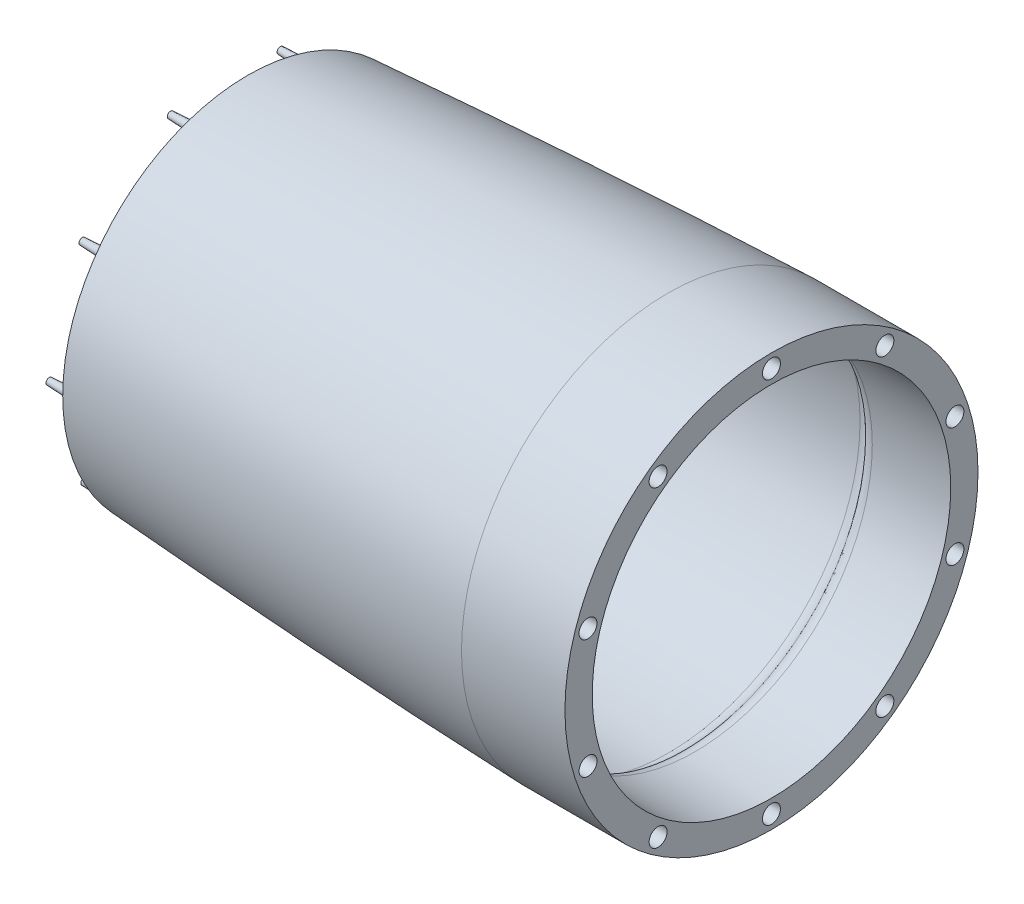
SolidWorks part; units mm, degrees
ref_plane "Front Plane" through (0, 0, 0) normal (0, 0, 1) x (1, 0, 0)
ref_plane "Top Plane" through (0, 0, 0) normal (0, 1, 0) x (1, 0, 0)
ref_plane "Right Plane" through (0, 0, 0) normal (1, 0, 0) x (0, 0, -1)
sketch "Sketch1" plane through (0, 0, 0) normal (0, 0, 1) x (1, 0, 0)
  line L2 (0, -76.2) -> (-921.7152, -76.2) construction
  line L3 (6.35, 6.35) -> (6.35, 0)
  line L4 (-259.8125, 11.4606) -> (6.35, 11.4606)
  line L5 (0, 0) -> (6.35, 0)
  line L6 (6.35, 6.35) -> (6.35, -76.2) construction
  line L7 (0, 0) -> (0, -76.2) construction
  line L8 (-921.7152, -58.5997) -> (-928.0652, -58.5997)
  line L9 (-928.0652, -58.5997) -> (-928.0652, -76.2) construction
  line L10 (-921.7152, -58.5997) -> (-921.7152, -76.2) construction
  line L11 (6.35, 11.4606) -> (6.35, 6.35)
  arc A0 (-254, 2.1118) -> (-248.4137, -0.891) centre (-248.6021, 5.4563) ccw
  arc A2 (-916.3053, -52.3197) -> (-921.7152, -58.5997) centre (-915.3652, -58.5997) ccw
  arc A4 (-254, 2.1118) -> (-259.6052, 5.114) centre (-259.3979, -1.2327) ccw
  arc A6 (-248.6021, 5.4563) -> (-248.6021, 5.4563) centre (-248.6021, 5.4563) ccw
  arc A7 (-248.6021, 5.4563) -> (-259.8125, 11.4606) centre (-259.3979, -1.2327) ccw
  arc A8 (-917.2454, -46.0396) -> (-928.0652, -58.5997) centre (-915.3652, -58.5997) ccw
  spline S0 degree 3 poles (0, 0) (-50.8, 0) (-101.6, 0) (-157.1824, 0) (-166.7471, 0) (-181.0943, 0) (-190.659, 0) (-199.5851, 0) (-207.8726, 0) (-220.3048, -0.155) (-228.5897, -0.3615) (-235.0947, -0.5237) (-239.8196, -0.6415) (-245.0466, -0.7915) (-247.9113, -0.876) (-248.4137, -0.891) knots 0.761574 0.761574 0.761574 0.761574 0.907842 0.907842 0.921611 0.935381 0.949151 0.949151 0.961082 0.973013 0.984944 0.984944 0.991748 0.998553 1 1 1 1
  spline S1 degree 1 poles (6.35, 6.35) (-248.6021, 5.4563) knots 0 0 1 1 construction
  spline S2 degree 3 poles (-259.6052, 5.114) (-267.1277, 4.8682) (-283.426, 4.2857) (-317.2703, 2.8805) (-361.13, 0.7112) (-431.2755, -3.372) (-501.3729, -8.2669) (-571.4145, -13.8917) (-623.9147, -18.4777) (-676.3803, -23.4393) (-728.8057, -28.7991) (-772.4536, -33.6275) (-807.3418, -37.7392) (-833.4907, -40.9589) (-859.6194, -44.3289) (-885.7239, -47.8693) (-904.6125, -50.5779) (-914.801, -52.0945) (-916.3053, -52.3197) knots 0.121539 0.121539 0.121539 0.121539 0.143123 0.168303 0.218664 0.269025 0.369746 0.420107 0.470467 0.520828 0.571189 0.62155 0.64673 0.67191 0.697091 0.722271 0.747451 0.751814 0.751814 0.751814 0.751814
  spline S3 degree 1 poles (-259.8125, 11.4606) (-917.2454, -46.0396) knots 0 0 1 1 construction
  spline S4 degree 3 poles (6.35, 6.35) (-14.881, 6.35) (-57.3424, 6.3506) (-110.4226, 6.3484) (-152.8795, 6.3528) (-179.4314, 6.3414) (-200.6356, 6.3648) (-216.6826, 6.282) (-232.6614, 5.8947) (-243.2867, 5.614) (-248.6021, 5.4563) knots 0.75548 0.75548 0.75548 0.75548 0.81661 0.87774 0.908305 0.93887 0.954152 0.969435 0.984717 1 1 1 1
  spline S5 degree 3 poles (-259.8125, 11.4606) (-287.3121, 10.5623) (-342.298, 8.1716) (-452.1401, 1.8335) (-589.2803, -8.5121) (-726.1766, -21.7709) (-835.4658, -34.5887) (-890.027, -41.9652) (-917.2454, -46.0396) knots 0.121539 0.121539 0.121539 0.121539 0.200324 0.279108 0.436676 0.594245 0.673029 0.751814 0.751814 0.751814 0.751814
revolve "Revolve1" add sketch "Sketch1" angle 360 about L2 region at (-124.3289, 8.8839, 0) region at (-3.0204, 3.175, 0)
ref_plane "Plane1" through (-215.9, 0, 0) normal (1, 0, 0) x (0, 0, -1)
sketch "Sketch2" plane through (-215.9, 0, 0) normal (1, 0, 0) x (0, 0, -1)
  circle A0 centre (0, -76.2) radius 87.6606 construction
  circle A1 centre (0, -76.2) radius 87.6606 construction
  circle A2 centre (0, -76.2) radius 110.1147
extrude "Cut-Extrude1" cut sketch "Sketch2" along normal through all contours A2 region at (-215.9, -76.2, 0)
ref_plane "Plane2" through (-438.15, 0, 0) normal (1, 0, 0) x (0, 0, -1)
sketch "Sketch5" plane through (-438.15, 0, 0) normal (1, 0, 0) x (0, 0, -1)
  circle A0 centre (0, -76.2) radius 87.6606 construction
  circle A1 centre (0, -76.2) radius 87.6606 construction
  circle A2 centre (0, -76.2) radius 128.8001
extrude "Cut-Extrude2" cut sketch "Sketch5" against normal through all
sketch "Sketch6" plane through (-215.9, 0, 0) normal (1, 0, 0) x (0, 0, -1)
  circle A0 centre (0, -76.2) radius 76.0918 construction
  circle A1 centre (0, -76.2) radius 87.6606 construction
  circle A2 centre (0, -76.2) radius 76.0918 construction
  circle A3 centre (0, -76.2) radius 87.6606 construction
  circle A4 centre (0, -76.2) radius 81.8762 construction
  circle A5 centre (0, 5.6762) radius 3.81
  circle A6 centre (48.1256, -9.9608) radius 3.81
  circle A7 centre (77.8689, -50.8989) radius 3.81
  circle A8 centre (77.8689, -101.5011) radius 3.81
  circle A9 centre (48.1256, -142.4392) radius 3.81
  circle A10 centre (0, -158.0762) radius 3.81
  circle A11 centre (-48.1256, -142.4392) radius 3.81
  circle A12 centre (-77.8689, -101.5011) radius 3.81
  circle A13 centre (-77.8689, -50.8989) radius 3.81
  circle A14 centre (-48.1256, -9.9608) radius 3.81
  point P29 (0, -76.2)
  dimension "D1" = 11.5687
  dimension "D2" = 5.7844
  dimension "D3" = 7.62
  dimension "D4" = 10
extrude "Cut-Extrude3" cut sketch "Sketch6" against normal blind 13.97
sketch "Sketch7" plane through (-438.15, 0, 0) normal (-1, 0, 0) x (0, 0, 1)
  line L0 (0, -76.2) -> (23.926, -4.6927) construction
  line L1 (0, -76.2) -> (0, 0) construction
  circle A0 centre (0, -76.2) radius 72.2219 construction
  circle A1 centre (0, -76.2) radius 78.586 construction
  circle A2 centre (0, -76.2) radius 72.2219 construction
  circle A3 centre (0, -76.2) radius 78.586 construction
  circle A4 centre (0, -76.2) radius 75.4039 construction
  circle A5 centre (23.926, -4.6927) radius 1.778
  circle A6 centre (61.3875, -32.4127) radius 1.778
  circle A7 centre (75.4011, -76.858) radius 1.778
  circle A8 centre (60.614, -121.052) radius 1.778
  circle A9 centre (22.6744, -148.114) radius 1.778
  circle A10 centre (-23.926, -147.7073) radius 1.778
  circle A11 centre (-61.3875, -119.9873) radius 1.778
  circle A12 centre (-75.4011, -75.542) radius 1.778
  circle A13 centre (-60.614, -31.348) radius 1.778
  circle A14 centre (-22.6744, -4.286) radius 1.778
  point P32 (0, -76.2)
  dimension "D1" = 6.364
  dimension "D2" = 3.182
  dimension "D3" = 3.556
  dimension "D4" = 18.5
  dimension "D5" = 10
extrude "Boss-Extrude2" add sketch "Sketch7" along normal blind 8.89 draft 2.5
